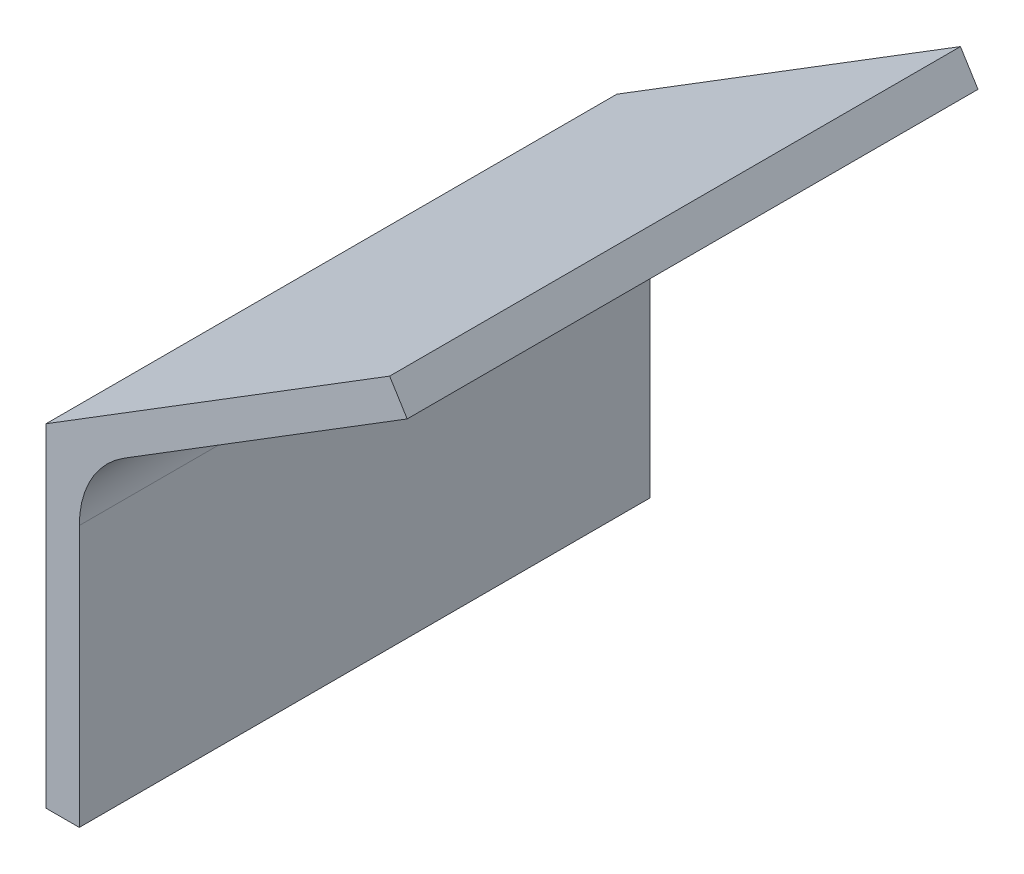
SolidWorks part; units mm, degrees
material "PLA"
ref_plane "Front Plane" through (0, 0, 0) normal (0, 0, 1) x (1, 0, 0)
ref_plane "Top Plane" through (0, 0, 0) normal (0, 1, 0) x (1, 0, 0)
ref_plane "Right Plane" through (0, 0, 0) normal (1, 0, 0) x (0, 0, -1)
sketch "Sketch1" plane through (0, 0, 0) normal (0, 0, 1) x (1, 0, 0)
  line L0 (0, 0) -> (72.2409, 44.7912)
  line L1 (0, 0) -> (0, -70)
  line L2 (7, -3.8962) -> (75.9296, 38.842)
  line L3 (7, -3.8962) -> (7, -70)
  line L4 (72.2409, 44.7912) -> (75.9296, 38.842)
  line L5 (0, -70) -> (7, -70)
  dimension "D1" = 85
  dimension "D2" = 70
  dimension "D3" = 121.8
  dimension "D4" = 7
extrude "Boss-Extrude1" add sketch "Sketch1" along normal mid plane 120
fillet "Fillet1" radius 20 1 edges at (7, -3.8962, 0)
